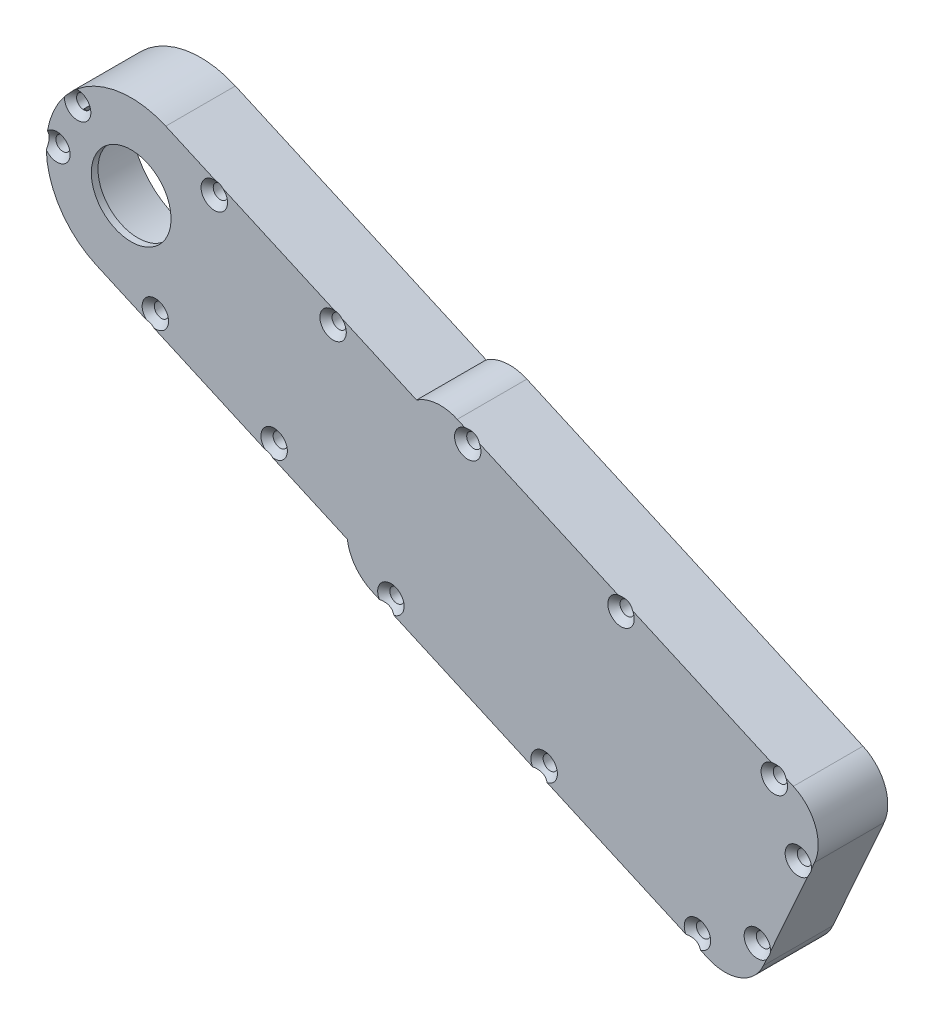
SolidWorks part; units mm, degrees
ref_plane "Front Plane" through (0, 0, 0) normal (0, 0, 1) x (1, 0, 0)
ref_plane "Top Plane" through (0, 0, 0) normal (0, 1, 0) x (1, 0, 0)
ref_plane "Right Plane" through (0, 0, 0) normal (1, 0, 0) x (0, 0, -1)
sketch "Sketch1" plane through (0, 0, 0) normal (0, 0, 1) x (1, 0, 0)
  line L0 (-21.9139, 59.5524) -> (-102.0156, 95.2596)
  line L1 (-111.7232, 94.3865) -> (-171.498, 121.0325)
  line L2 (-187.9877, 84.0414) -> (-128.2129, 57.3954)
  line L3 (-122.3733, 49.5916) -> (-42.2716, 13.8844)
  line L4 (-29.0664, 18.9465) -> (-16.8519, 46.3473)
  line L5 (-179.7428, 102.5369) -> (-198.2384, 110.7818) construction
  line L6 (-179.7428, 102.5369) -> (-197.449, 103.7832) construction
  line L7 (-179.7428, 102.5369) -> (-192.5055, 114.8729) construction
  arc A0 (-16.8519, 46.3473) -> (-21.9139, 59.5524) centre (-25.9855, 50.4188) ccw
  arc A1 (-102.0156, 95.2596) -> (-111.7232, 94.3865) centre (-106.0872, 86.126) ccw
  arc A2 (-171.498, 121.0325) -> (-187.9877, 84.0414) centre (-179.7428, 102.5369) ccw
  arc A3 (-128.2129, 57.3954) -> (-122.3733, 49.5916) centre (-118.3017, 58.7252) ccw
  arc A4 (-42.2716, 13.8844) -> (-29.0664, 18.9465) centre (-38.2, 23.018) ccw
  circle A5 centre (-99.5171, 91.4087) radius 1.7
  circle A6 centre (-62.9827, 75.1226) radius 1.7
  circle A7 centre (-26.4483, 58.8365) radius 1.7
  circle A8 centre (-20.7221, 44.7879) radius 1.7
  circle A9 centre (-30.4937, 22.8673) radius 1.7
  circle A10 centre (-44.7701, 17.7353) radius 1.7
  circle A11 centre (-81.3045, 34.0214) radius 1.7
  circle A12 centre (-117.8389, 50.3075) radius 1.7
  circle A13 centre (-131.6182, 99.9706) radius 1.7
  circle A14 centre (-145.665, 68.4596) radius 1.7
  circle A15 centre (-173.9792, 81.0813) radius 1.7
  circle A16 centre (-159.9324, 112.5923) radius 1.7
  circle A17 centre (-192.5055, 114.8729) radius 1.7
  circle A18 centre (-197.449, 103.7832) radius 1.7
  dimension "D1" = 3.4
  dimension "D2" = 3.4
  dimension "D3" = 3.4
  dimension "D4" = 3.4
  dimension "D5" = 3.4
  dimension "D6" = 3.4
  dimension "D12" = 20.25
  dimension "D16" = 10
  dimension "D17" = 10
  dimension "D18" = 10
  dimension "D19" = 10
  dimension "D25" = 2.9
  dimension "D26" = 2.9
  dimension "D29" = 93.85
  dimension "D30" = 53.85
  dimension "D31" = 93.85
  dimension "D32" = 13.85
  dimension "D33" = 20
  dimension "D35" = 17.75
  dimension "D36" = 17.75
  dimension "D7" = 106.211
  dimension "D8" = 87.7
  dimension "D9" = 50
  dimension "D10" = 4.75
  dimension "D11" = 4.75
  dimension "D13" = 40.5
  dimension "D14" = 106.211
  dimension "D15" = 87.7
  dimension "D20" = 106.211
  dimension "D21" = 171.6559
  dimension "D22" = 30
  dimension "D23" = 10
  dimension "D24" = 10
  dimension "D27" = 13.85
  dimension "D28" = 53.85
  dimension "D34" = 20
extrude "Boss-Extrude1" add sketch "Sketch1" along normal blind 1.5875
sketch "Sketch2" plane through (0, 0, 0) normal (0, 0, -1) x (-1, 0, 0)
  circle A0 centre (179.7428, 102.5369) radius 9.5
  dimension "D1" = 19
extrude "Cut-Extrude1" cut sketch "Sketch2" against normal through all
hole_wizard "CSK for M3 Flat Head Machine Screw1" positions "Sketch4" profile "Sketch3" countersink size "M3" standard "ANSI Metric" end condition through all
sketch "Sketch4" plane through (0, 0, 1.5875) normal (0, 0, 1) x (1, 0, 0)
  point P0 (-192.5055, 114.8729)
  point P3 (-197.449, 103.7832)
  point P6 (-173.9792, 81.0813)
  point P9 (-145.665, 68.4596)
  point P12 (-117.8389, 50.3075)
  point P15 (-81.3045, 34.0214)
  point P18 (-44.7701, 17.7353)
  point P21 (-30.4937, 22.8673)
  point P24 (-20.7221, 44.7879)
  point P27 (-26.4483, 58.8365)
  point P30 (-62.9827, 75.1226)
  point P33 (-99.5171, 91.4087)
  point P36 (-131.6182, 99.9706)
  point P39 (-159.9324, 112.5923)
sketch "Sketch3" plane through (-192.5055, 114.8729, 1.5875) normal (1, 0, 0) x (0, -1, 0)
  line L0 (0, 0) -> (0, 1.5875)
  line L1 (0, 1.5875) -> (1.7, 1.5875)
  line L2 (1.7, 1.5875) -> (1.7, 1.45)
  line L3 (1.7, 1.45) -> (3.15, 0)
  line L5 (3.15, 0) -> (0, 0)
  line L6 (-1.7, 1.45) -> (-3.15, 0) construction
  line L11 (0, -6.35) -> (0, 107.95) construction
  dimension "Thru Hole Dia." = 3.4
  dimension "Thru Hole Depth" = 1.5875
  dimension "Near C'Sink Dia." = 6.3
  dimension "Near C'Sink Angle" = 90
sketch "Sketch5" plane through (0, 0, 0) normal (0, 0, -1) x (-1, 0, 0)
  line L0 (107.7718, 87.1507) -> (173.5338, 116.4657)
  line L1 (120.19, 59.2932) -> (185.9519, 88.6082)
  line L2 (19.3829, 52.9498) -> (105.8416, 91.4909)
  line L3 (122.1239, 54.9548) -> (35.669, 16.4154)
  line L4 (107.7718, 87.1507) -> (136.476, 22.7588) construction
  line L5 (16.8519, 46.3473) -> (29.0664, 18.9465)
  line L6 (42.2716, 13.8844) -> (122.3733, 49.5916)
  line L7 (128.2129, 57.3954) -> (187.9877, 84.0414)
  line L8 (171.498, 121.0325) -> (111.7232, 94.3865)
  line L9 (102.0156, 95.2596) -> (21.9139, 59.5524)
  line L10 (16.8519, 46.3473) -> (29.0664, 18.9465)
  line L11 (42.2716, 13.8844) -> (122.3733, 49.5916)
  line L12 (128.2129, 57.3954) -> (187.9877, 84.0414)
  line L13 (171.498, 121.0325) -> (111.7232, 94.3865)
  line L14 (102.0156, 95.2596) -> (21.9139, 59.5524)
  line L15 (35.669, 16.4154) -> (19.3829, 52.9498)
  line L16 (107.7718, 87.1507) -> (105.8416, 91.4909)
  line L17 (120.19, 59.2932) -> (122.1239, 54.9548)
  circle A0 centre (20.7221, 44.7879) radius 1.7 construction
  circle A1 centre (30.4937, 22.8673) radius 1.7 construction
  circle A2 centre (44.7701, 17.7353) radius 1.7 construction
  circle A3 centre (81.3045, 34.0214) radius 1.7 construction
  circle A4 centre (117.8389, 50.3075) radius 1.7 construction
  arc A5 (21.9139, 59.5524) -> (16.8519, 46.3473) centre (25.9855, 50.4188) ccw
  arc A6 (29.0664, 18.9465) -> (42.2716, 13.8844) centre (38.2, 23.018) ccw
  arc A7 (122.3733, 49.5916) -> (128.2129, 57.3954) centre (118.3017, 58.7252) ccw
  arc A8 (187.9877, 84.0414) -> (171.498, 121.0325) centre (179.7428, 102.5369) ccw
  arc A9 (111.7232, 94.3865) -> (102.0156, 95.2596) centre (106.0872, 86.126) ccw
  arc A10 (21.9139, 59.5524) -> (16.8519, 46.3473) centre (25.9855, 50.4188) ccw
  arc A11 (29.0664, 18.9465) -> (42.2716, 13.8844) centre (38.2, 23.018) ccw
  arc A12 (122.3733, 49.5916) -> (128.2129, 57.3954) centre (118.3017, 58.7252) ccw
  arc A13 (187.9877, 84.0414) -> (171.498, 121.0325) centre (179.7428, 102.5369) ccw
  arc A14 (111.7232, 94.3865) -> (102.0156, 95.2596) centre (106.0872, 86.126) ccw
  circle A15 centre (145.665, 68.4596) radius 1.7 construction
  circle A16 centre (173.9792, 81.0813) radius 1.7 construction
  circle A17 centre (197.449, 103.7832) radius 1.7 construction
  circle A18 centre (192.5055, 114.8729) radius 1.7 construction
  circle A19 centre (159.9324, 112.5923) radius 1.7 construction
  circle A20 centre (131.6182, 99.9706) radius 1.7 construction
  circle A21 centre (99.5171, 91.4087) radius 1.7 construction
  circle A22 centre (62.9827, 75.1226) radius 1.7 construction
  circle A23 centre (26.4483, 58.8365) radius 1.7 construction
  circle A24 centre (20.7221, 44.7879) radius 1.7
  circle A25 centre (30.4937, 22.8673) radius 1.7
  circle A26 centre (44.7701, 17.7353) radius 1.7
  circle A27 centre (81.3045, 34.0214) radius 1.7
  circle A28 centre (117.8389, 50.3075) radius 1.7
  circle A29 centre (145.665, 68.4596) radius 1.7
  circle A30 centre (173.9792, 81.0813) radius 1.7
  circle A31 centre (197.449, 103.7832) radius 1.7
  circle A32 centre (192.5055, 114.8729) radius 1.7
  circle A33 centre (159.9324, 112.5923) radius 1.7
  circle A34 centre (131.6182, 99.9706) radius 1.7
  circle A35 centre (99.5171, 91.4087) radius 1.7
  circle A36 centre (62.9827, 75.1226) radius 1.7
  circle A37 centre (26.4483, 58.8365) radius 1.7
  arc A38 (185.9519, 88.6082) -> (173.5338, 116.4657) centre (179.7428, 102.5369) ccw
  dimension "D2" = 5
  dimension "D5" = 72
  dimension "D3" = 5
  dimension "D4" = 5
  dimension "D6" = 72
  dimension "D7" = 5
  dimension "D8" = 94.66
  dimension "D1" = 0
extrude "Boss-Extrude2" add sketch "Sketch5" along normal blind 15
fillet "Fillet1" radius 5 2 edges at (-120.19, 59.2932, -7.5) (-107.7718, 87.1507, -7.5)
fillet "Fillet2" radius 3 2 edges at (-122.1239, 54.9548, -7.5) (-105.8416, 91.4909, -7.5)
fillet "Fillet3" radius 5 2 edges at (-35.669, 16.4154, -7.5) (-19.3829, 52.9498, -7.5)
sketch "Sketch6" plane through (0, 0, -15) normal (0, 0, -1) x (-1, 0, 0)
  line L0 (27.5259, 34.6826) -> (179.7428, 102.5369) construction
  line L1 (21.4187, 48.383) -> (33.6332, 20.9822) construction
  line L2 (16.8519, 46.3473) -> (29.0664, 18.9465) construction
  circle A0 centre (37.1162, 38.9577) radius 14
  dimension "D1" = 28
  dimension "D2" = 15.5
extrude "Cut-Extrude2" cut sketch "Sketch6" against normal up to surface (15 mm away) up to face at (-98.3335, 66.2468, 0)
sketch "Sketch7" plane through (0, 0, -15) normal (0, 0, -1) x (-1, 0, 0)
  circle A0 centre (179.7428, 102.5369) radius 16.75
  dimension "D1" = 33.5
extrude "Cut-Extrude3" cut sketch "Sketch7" against normal up to surface (15 mm away) up to face at (-87.9898, 61.6358, 0)
